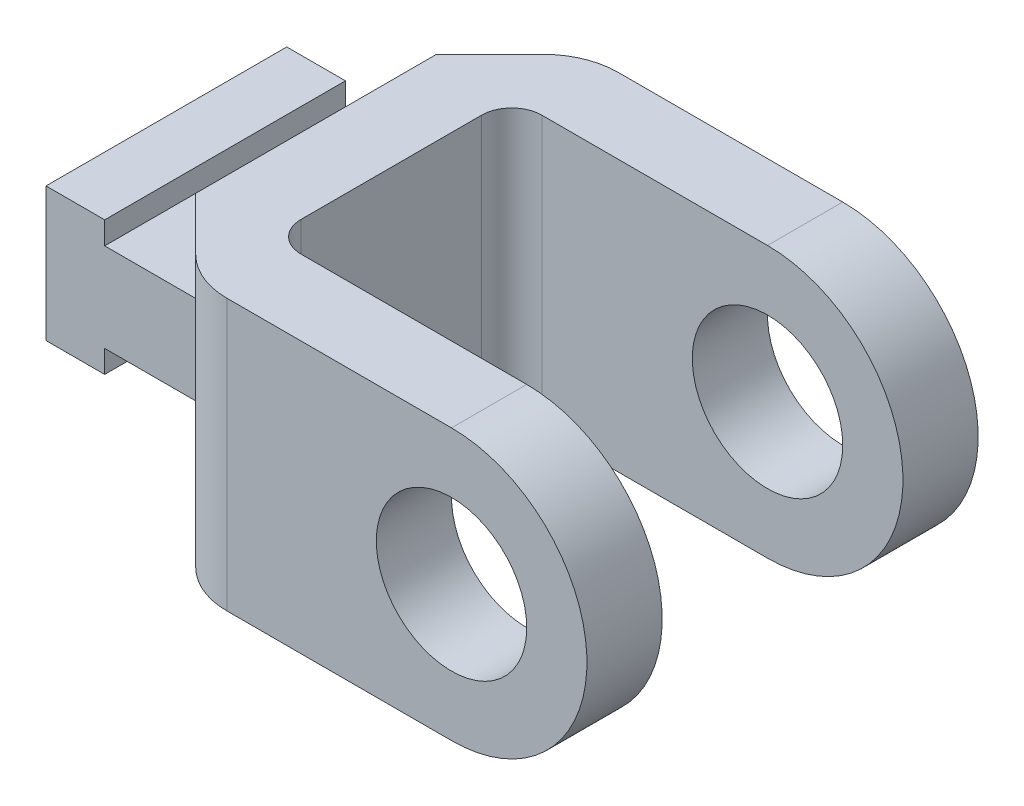
SolidWorks part; units mm, degrees
ref_plane "Front Plane" through (0, 0, 0) normal (0, 0, 1) x (1, 0, 0)
ref_plane "Top Plane" through (0, 0, 0) normal (0, 1, 0) x (1, 0, 0)
ref_plane "Right Plane" through (0, 0, 0) normal (1, 0, 0) x (0, 0, -1)
sketch "Sketch1" plane through (0, 0, 0) normal (0, 0, 1) x (1, 0, 0)
  line L0 (-6.6738, 0) -> (8.2152, 0) construction
  line L22 (1.25, -4.5) -> (-1.25, -4.5)
  line L25 (1.25, -4.5) -> (1.25, 4.5)
  line L26 (1.25, 4.5) -> (-1.25, 4.5)
  line L28 (1.25, -4.5) -> (-1.25, 4.5) construction
  line L29 (1.25, 4.5) -> (-1.25, -4.5) construction
  line L36 (-1.25, -4.5) -> (-1.25, 4.5)
  point P0 (0, 0)
  point P3 (0, 0)
  point P6 (1.5718, 1.475)
  point P9 (1.5718, -1.475)
  dimension "D2" = 2.5
  dimension "D3" = 9
extrude "Boss-Extrude1" add sketch "Sketch1" along normal blind 8 contours L26 L36 L22 L25
ref_plane "Notch Plane" through (0, 0, 4) normal (0, 0, 1) x (1, 0, 0)
sketch "Sketch6" plane through (0, 0, 4) normal (0, 0, 1) x (1, 0, 0)
  line L0 (4.0863, 0) -> (-8.8455, 0) construction
  line L1 (-1.25, -4.5) -> (-1.25, 4.5) construction
  line L2 (-4.275, -1.475) -> (-1.25, -1.475)
  line L4 (-4.275, 1.475) -> (-1.25, 1.475)
  line L5 (-1.25, -1.475) -> (-1.25, 1.475)
  line L6 (-4.275, -1.475) -> (-1.25, 1.475) construction
  line L7 (-4.275, 1.475) -> (-1.25, -1.475) construction
  line L8 (-4.275, 1.475) -> (-4.275, 2.225)
  line L9 (-6.225, -2.225) -> (-4.275, -2.225)
  line L10 (-6.225, -2.225) -> (-6.225, 2.225)
  line L11 (-6.225, 2.225) -> (-4.275, 2.225)
  line L12 (-4.275, -2.225) -> (-4.275, -1.475)
  line L13 (-6.225, -2.225) -> (-4.275, 2.225) construction
  line L14 (-6.225, 2.225) -> (-4.275, -2.225) construction
  point P3 (-2.7625, 0)
  point P10 (-5.25, 0)
  dimension "D1" = 2.95
  dimension "D2" = 3.025
  dimension "D3" = 4.45
  dimension "D4" = 1.95
extrude "Boss-Extrude4" add sketch "Sketch6" along normal through all and the other way through all contours L2 L5 L4 L8 L11 L10 L9 L12
sketch "Sketch2" plane through (0, 0, 0) normal (0, 0, 1) x (1, 0, 0)
  line L0 (-4.6464, 0) -> (18.6847, 0) construction
  line L3 (9.75, -4.5) -> (-1.25, -4.5)
  line L5 (9.75, 4.5) -> (-1.25, 4.5)
  line L6 (-1.25, -4.5) -> (-1.25, 4.5)
  line L7 (12.7356, -3.3669) -> (-1.25, 4.5) construction
  line L8 (12.7356, 3.3669) -> (-1.25, -4.5) construction
  arc A0 (9.75, -4.5) -> (9.75, 4.5) centre (9.75, 0) ccw
  circle A1 centre (9.75, 0) radius 2.5
  circle A2 centre (9.75, 0) radius 7.5 construction
  point P5 (6.75, 0)
  point P7 (14.25, 0)
  dimension "D3" = 5
  dimension "D4" = 15
  dimension "D1" = 15.5
  dimension "D2" = 9
extrude "Boss-Extrude3" add sketch "Sketch2" against normal blind 2.5
sketch "Sketch5" plane through (0, 4.5, 0) normal (0, 1, 0) x (1, 0, 0)
  line L0 (1.25, 0) -> (1.25, 4.091) construction
  line L1 (9.75, 2.5) -> (-1.25, 2.5) construction
  line L6 (-1.25, 2.5) -> (1.25, 2.5)
  line L7 (-1.25, 2.5) -> (-1.25, 0)
  line L8 (-1.25, 0) -> (1.25, 2.5)
  point P3 (1.25, 2.5)
  point P8 (-1.25, 0)
extrude "Cut-Extrude2" cut sketch "Sketch5" against normal through all and the other way through all
fillet "Fillet5" radius 1 1 edges at (1.25, 0, 0)
fillet "Fillet6" radius 2.5 1 edges at (1.25, 0, -2.5)
ref_plane "Plane1" through (0, 0, 4) normal (0, 0, -1) x (-1, 0, 0)
mirror "Mirror2" about plane through (0, 0, 4) normal (0, 0, -1) of "Cut-Extrude2", "Fillet6", "Fillet5", "Boss-Extrude3"
